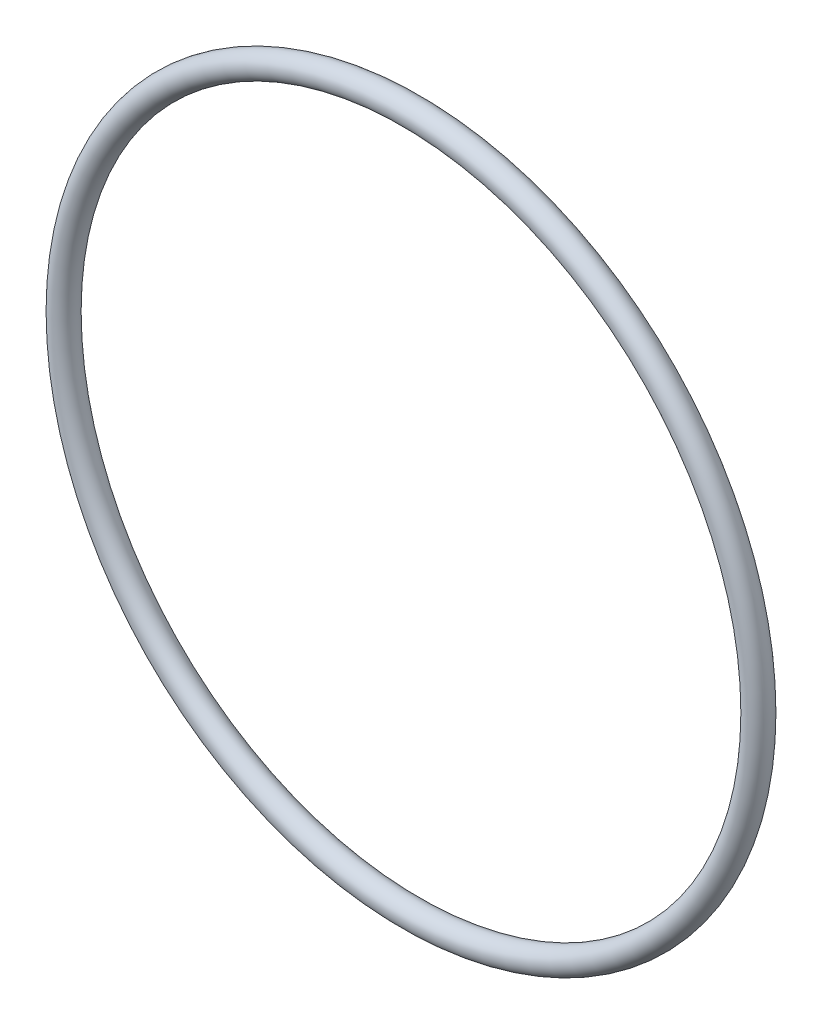
SolidWorks part; units mm, degrees
ref_plane "Płaszczyzna przednia" through (0, 0, 0) normal (0, 0, 1) x (1, 0, 0)
ref_plane "Płaszczyzna górna" through (0, 0, 0) normal (0, 1, 0) x (1, 0, 0)
ref_plane "Płaszczyzna prawa" through (0, 0, 0) normal (1, 0, 0) x (0, 0, -1)
sketch "Szkic1" plane through (0, 0, 0) normal (1, 0, 0) x (0, 0, -1)
  line L0 (-409.7655, 0) -> (287.8541, 0) construction
  circle A0 centre (0, 42) radius 1.5
  dimension "D1" = 3
  dimension "D2" = 42
revolve "Obrót1" add sketch "Szkic1" angle 360 about L0
ref_axis "Oś1" through (0, 0, -1.65) along (0, 0, 1)
